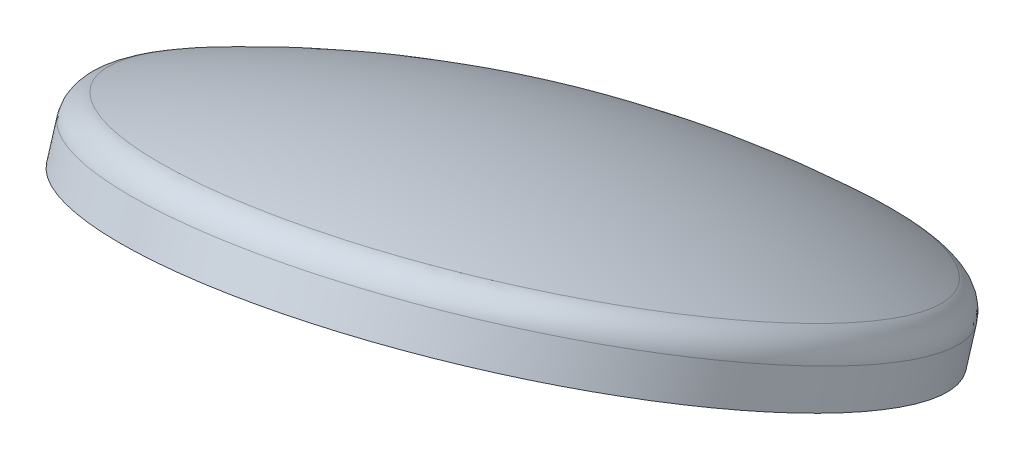
SolidWorks part; units mm, degrees
material "AISI 304"
ref_plane "Front Plane" through (0, 0, 0) normal (0, 0, 1) x (1, 0, 0)
ref_plane "Top Plane" through (0, 0, 0) normal (0, 1, 0) x (1, 0, 0)
ref_plane "Right Plane" through (0, 0, 0) normal (1, 0, 0) x (0, 0, -1)
sketch "Sketch1" plane through (-170.1265, -378.4626, 173.8923) normal (-0.9865, -0.1477, -0.0702) x (-0.1242, 0.3971, 0.9093)
  line L0 (-28.9646, 456.2779) -> (201.4134, 456.2779) construction
  line L1 (-28.9646, 456.2779) -> (-28.9646, 532.4779) construction
  line L2 (201.4134, 456.2779) -> (201.4134, 478.6032)
  line L3 (-28.9646, 532.4779) -> (228.6, 532.4779) construction
  line L4 (204.5884, 456.2779) -> (204.5884, 494.3365) construction
  line L5 (204.5884, 456.2779) -> (204.5884, 480.8757)
  line L6 (201.4134, 456.2779) -> (204.5884, 456.2779)
  line L7 (-28.9646, 535.6529) -> (-28.9646, 532.4779)
  line L8 (201.4134, 456.2779) -> (201.4134, 494.3365) construction
  arc A0 (-28.9646, 532.4779) -> (188.4759, 496.6459) centre (-28.9646, -145.1903) cw
  arc A1 (-28.9646, 532.4779) -> (201.2295, 492.1831) centre (-28.9646, -145.1903) cw construction
  arc A2 (-28.9646, 535.6529) -> (204.5884, 494.3411) centre (-28.9646, -145.1903) cw construction
  arc A3 (-28.9646, 535.6529) -> (191.713, 498.8973) centre (-28.9646, -145.1903) cw
  arc A4 (201.4134, 494.3365) -> (201.2295, 492.1831) centre (188.7134, 494.3365) ccw construction
  arc A5 (204.5884, 494.3365) -> (204.5884, 494.3411) centre (188.7134, 494.3365) ccw construction
  arc A6 (201.4134, 478.6032) -> (188.4759, 496.6459) centre (182.3634, 478.6032) ccw
  arc A7 (191.713, 498.8973) -> (204.5884, 480.8757) centre (185.5384, 480.8757) cw
  spline S1 degree 1 poles (201.4134, 456.2779) (201.4134, 492.1166) knots 0 0 1 1 construction
  point P0 (0, 0)
  dimension "D3" = 19.05
  dimension "D1" = 76.2
  dimension "D2" = 230.378
  dimension "D4" = 3.175
revolve "Revolve1" add sketch "Sketch1" angle 360 about L7
ref_axis "Axis1" through (-214.8479, 21.2961, -38.638) along (-0.1064, 0.9058, -0.4101)
ref_plane "Plane1" through (-191.898, 0, 49.7989) normal (0.9679, 0, -0.2512) x (-0.2512, 0, -0.9679)
